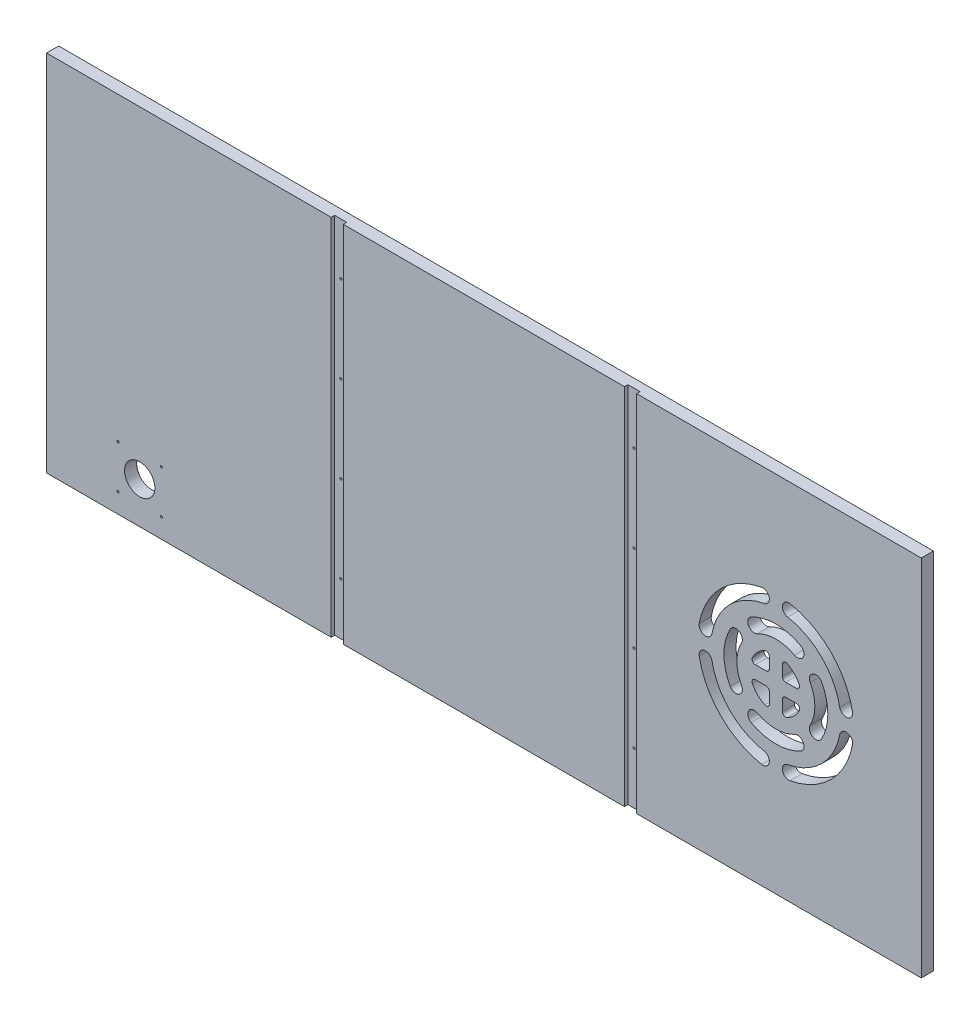
SolidWorks part; units mm, degrees
material "Pine"
ref_plane "Front Plane" through (0, 0, 0) normal (0, 0, 1) x (1, 0, 0)
ref_plane "Top Plane" through (0, 0, 0) normal (0, 1, 0) x (1, 0, 0)
ref_plane "Right Plane" through (0, 0, 0) normal (1, 0, 0) x (0, 0, -1)
sketch "Sketch1" plane through (0, 0, 0) normal (0, 0, 1) x (1, 0, 0)
  line L0 (8932.6508, -5243.5125) -> (10226.1458, -5243.5125)
  line L1 (9086.3208, -4722.0918) -> (10222.9708, -4853.7812)
  line L2 (8914.8708, -6342.0625) -> (10197.5708, -6342.0625)
  line L3 (8914.8708, -5808.6625) -> (10197.5708, -5808.6625)
  line L4 (8919.6333, -5253.0375) -> (10218.2083, -5253.0375)
  line L5 (9134.2633, -4656.1375) -> (9134.2633, -4638.3575)
  line L6 (9091.0833, -4638.3575) -> (9134.2633, -4638.3575)
  line L7 (9091.0833, -4567.2375) -> (9091.0833, -4638.3575)
  line L8 (9134.2633, -4656.1375) -> (9581.3033, -4656.1375)
  line L9 (9091.0833, -4567.2375) -> (9624.4833, -4567.2375)
  line L10 (9581.3033, -4656.1375) -> (9581.3033, -4638.3575)
  line L11 (9581.3033, -4638.3575) -> (9624.4833, -4638.3575)
  line L12 (9624.4833, -4567.2375) -> (9624.4833, -4638.3575)
  line L13 (8932.6508, -5225.7325) -> (9344.9775, -5225.7325)
  line L14 (8932.6508, -5256.2125) -> (8932.6508, -5243.5125)
  line L15 (8911.6958, -5256.2125) -> (8932.6508, -5256.2125)
  line L16 (8914.8708, -4722.0918) -> (9086.3208, -4722.0918)
  line L17 (8911.6958, -4715.5913) -> (8932.6508, -4715.5913)
  line L18 (8914.8708, -6342.0625) -> (8914.8708, -5808.6625)
  line L19 (12082.9917, -4722.0918) -> (10946.3417, -4853.7812)
  line L20 (12236.6617, -5243.5125) -> (10943.1667, -5243.5125)
  line L21 (10951.1042, -5253.0375) -> (12249.6792, -5253.0375)
  line L22 (10838.3917, -5656.2625) -> (11308.2917, -5656.2625)
  line L23 (10838.3917, -5719.7625) -> (11308.2917, -5719.7625)
  line L24 (10838.3917, -5742.5368) -> (11308.2917, -5742.5368)
  line L25 (10806.6417, -6342.0625) -> (11340.0417, -6342.0625)
  line L26 (10803.4667, -6335.7125) -> (11343.2167, -6335.7125)
  line L27 (10803.4667, -6317.9325) -> (11343.2167, -6317.9325)
  line L28 (10943.1667, -5225.7325) -> (11376.4483, -5225.7325)
  line L29 (11506.7292, -4754.5625) -> (10806.6417, -4827.5875)
  line L30 (11506.7292, -4567.2375) -> (11506.7292, -4754.5625)
  line L31 (10806.6417, -4567.2375) -> (10806.6417, -4827.5875)
  line L32 (10806.6417, -4567.2375) -> (11506.7292, -4567.2375)
  line L33 (10235.6708, -6329.3625) -> (10245.1958, -6329.3625)
  line L34 (10245.1958, -6329.3625) -> (10254.7208, -6278.5625)
  line L35 (10302.3458, -6329.3625) -> (10311.8708, -6278.5625)
  line L36 (10302.3458, -6329.3625) -> (10292.8208, -6329.3625)
  line L37 (10245.1958, -5821.3625) -> (10254.7208, -5872.1625)
  line L38 (10235.6708, -5821.3625) -> (10245.1958, -5821.3625)
  line L39 (10292.8208, -5821.3625) -> (10302.3458, -5821.3625)
  line L40 (10302.3458, -5821.3625) -> (10311.8708, -5872.1625)
  line L41 (10235.6708, -5821.3625) -> (10235.6708, -6329.3625)
  line L42 (10254.7208, -5872.1625) -> (10254.7208, -6278.5625)
  line L43 (10311.8708, -5872.1625) -> (10311.8708, -6278.5625)
  line L44 (10292.8208, -5821.3625) -> (10292.8208, -6329.3625)
  line L45 (8932.6508, -5225.7325) -> (8932.6508, -4715.5913)
  line L46 (8911.6958, -4715.5913) -> (8911.6958, -5256.2125)
  line L47 (8914.8708, -5248.275) -> (8914.8708, -4722.0918)
  line L48 (8919.6333, -5253.0375) -> (8914.8708, -5248.275)
  line L49 (8914.8708, -5145.0875) -> (8937.426, -5145.0875)
  line L50 (8914.8708, -5202.2375) -> (8937.426, -5202.2375)
  line L51 (10838.3917, -5656.2625) -> (10838.3917, -5719.7625)
  line L52 (10832.0417, -5736.1868) -> (10856.1717, -5736.1868)
  line L53 (10806.6417, -6342.0625) -> (10806.6417, -5818.7368)
  line L54 (10832.0417, -5649.9125) -> (10856.1717, -5649.9125)
  line L55 (10832.0417, -5726.1125) -> (10856.1717, -5726.1125)
  line L56 (10806.6417, -5818.7368) -> (10833.9015, -5818.7368)
  line L57 (10832.0417, -5806.0442) -> (10851.6815, -5806.0442)
  line L58 (10856.1717, -5801.5541) -> (10856.1717, -5736.1868)
  line L59 (10838.3917, -5814.2467) -> (10838.3917, -5742.5368)
  line L60 (10832.0417, -5806.0442) -> (10832.0417, -5736.1868)
  line L61 (10803.4667, -6317.9325) -> (10803.4667, -6335.7125)
  line L62 (10197.5708, -5808.6625) -> (10197.5708, -6342.0625)
  line L63 (9762.3842, -6348.4125) -> (9762.3842, -5802.3125)
  line L64 (9780.1642, -6348.4125) -> (9762.3842, -6348.4125)
  line L65 (9780.1642, -5802.3125) -> (9780.1642, -6348.4125)
  line L66 (9762.3842, -5802.3125) -> (9780.1642, -5802.3125)
  line L67 (9332.2775, -6348.4125) -> (9332.2775, -5802.3125)
  line L68 (9332.2775, -6348.4125) -> (9350.0575, -6348.4125)
  line L69 (9350.0575, -5802.3125) -> (9350.0575, -6348.4125)
  line L70 (9332.2775, -5802.3125) -> (9350.0575, -5802.3125)
  line L71 (9993.8374, -6061.075) -> (9993.8374, -6045.2418)
  line L72 (9998.5999, -6065.8375) -> (10014.4331, -6065.8375)
  line L73 (9998.5999, -6084.8875) -> (10014.4331, -6084.8875)
  line L74 (9993.8374, -6105.4832) -> (9993.8374, -6089.65)
  line L75 (9974.7874, -6105.4832) -> (9974.7874, -6089.65)
  line L76 (9954.1917, -6084.8875) -> (9970.0249, -6084.8875)
  line L77 (9974.7874, -6061.075) -> (9974.7874, -6045.2418)
  line L78 (9954.1917, -6065.8375) -> (9970.0249, -6065.8375)
  line L79 (10793.9417, -6237.2875) -> (10816.4969, -6237.2875)
  line L80 (10793.9417, -6294.4375) -> (10816.4969, -6294.4375)
  line L81 (10856.1717, -5649.9125) -> (10856.1717, -5726.1125)
  line L82 (10832.0417, -5726.1125) -> (10832.0417, -5649.9125)
  line L83 (10226.1458, -5225.7325) -> (10226.1458, -5243.5125)
  line L84 (10205.1908, -5257.8) -> (10205.1908, -4844.2499)
  line L85 (10230.9083, -4844.2499) -> (10230.9083, -5257.8)
  line L86 (10205.1908, -5257.8) -> (10230.9083, -5257.8)
  line L87 (10205.1908, -4844.2499) -> (10230.9083, -4844.2499)
  line L88 (10946.3417, -5176.8375) -> (10968.8969, -5176.8375)
  line L89 (9349.4676, -5141.9125) -> (9358.2674, -5141.9125)
  line L90 (10946.3417, -5119.6875) -> (10968.8969, -5119.6875)
  line L91 (9929.011, -4660.9635) -> (10066.0807, -4660.9635)
  line L92 (9929.011, -4678.7435) -> (10066.0807, -4678.7435)
  line L93 (10943.1667, -5225.7325) -> (10943.1667, -5243.5125)
  line L94 (10946.3417, -5248.275) -> (10951.1042, -5253.0375)
  line L95 (10946.3417, -5257.8063) -> (10946.3417, -4849.0188)
  line L96 (10964.1217, -5257.8) -> (10964.1217, -4844.2499)
  line L97 (10938.4042, -4844.2499) -> (10938.4042, -5257.8)
  line L98 (10938.4042, -5257.8) -> (10964.1217, -5257.8)
  line L99 (10964.1217, -4844.2499) -> (10938.4042, -4844.2499)
  line L100 (10344.8908, -4560.8875) -> (10369.0208, -4560.8875)
  line L101 (10344.8908, -4560.8875) -> (10369.0208, -4560.8875)
  line L102 (10800.2917, -4560.8875) -> (10824.4217, -4560.8875)
  line L103 (10200.4156, -5119.6875) -> (10222.9708, -5119.6875)
  line L104 (10200.4156, -5176.8375) -> (10222.9708, -5176.8375)
  line L105 (9344.9775, -5146.4026) -> (9344.9775, -5225.7325)
  line L106 (10344.8908, -4560.8875) -> (10344.8908, -4833.9375)
  line L107 (9792.8642, -5225.7325) -> (9792.8642, -5146.4026)
  line L108 (9362.7575, -5225.7325) -> (9775.0842, -5225.7325)
  line L109 (9680.3633, -4761.8396) -> (9680.3633, -4559.9604)
  line L110 (9656.2333, -4559.9604) -> (9680.3633, -4559.9604)
  line L111 (9656.2333, -4761.8396) -> (9680.3633, -4761.8396)
  line L112 (9656.2333, -4761.8396) -> (9656.2333, -4559.9604)
  line L113 (9779.5743, -5141.9125) -> (9788.374, -5141.9125)
  line L114 (10070.5708, -4665.4536) -> (10070.5708, -4674.2534)
  line L115 (9924.5208, -4674.2534) -> (9924.5208, -4665.4536)
  line L116 (12127.4417, -6188.3925) -> (12205.5015, -6188.3925)
  line L117 (12209.9917, -6170.6125) -> (12209.9917, -6183.9024)
  line L118 (9792.8642, -5225.7325) -> (10226.1458, -5225.7325)
  line L119 (9662.5833, -4754.5625) -> (10362.6708, -4827.5875)
  line L120 (9662.5833, -4567.2375) -> (9662.5833, -4754.5625)
  line L121 (10362.6708, -4567.2375) -> (10362.6708, -4827.5875)
  line L122 (9662.5833, -4567.2375) -> (10362.6708, -4567.2375)
  line L123 (10824.4217, -4833.9375) -> (10800.2917, -4833.9375)
  line L124 (10800.2917, -4833.9375) -> (10800.2917, -4560.8875)
  line L125 (10824.4217, -4560.8875) -> (10824.4217, -4833.9375)
  line L126 (10344.8908, -4833.9375) -> (10369.0208, -4833.9375)
  line L127 (10369.0208, -4833.9375) -> (10369.0208, -4560.8875)
  line L128 (10222.9708, -5248.275) -> (10218.2083, -5253.0375)
  line L129 (10222.9708, -5257.8063) -> (10222.9708, -4849.0188)
  line L130 (11734.6544, -5701.375) -> (11739.2301, -5701.375)
  line L131 (9362.7575, -5225.7325) -> (9362.7575, -5146.4026)
  line L132 (9775.0842, -5146.4026) -> (9775.0842, -5225.7325)
  line L133 (11761.3864, -5701.375) -> (11756.8282, -5701.375)
  line L134 (11734.6544, -5693.755) -> (11739.2301, -5693.755)
  line L135 (11761.4039, -5693.755) -> (11756.8282, -5693.755)
  line L136 (11734.6544, -5701.375) -> (11739.2301, -5701.375)
  line L137 (11744.3462, -5721.3024) -> (11744.3462, -5706.4179)
  line L138 (11751.7122, -5721.3024) -> (11751.7122, -5706.4179)
  line L139 (11740.0917, -6170.6125) -> (11740.0917, -6183.9024)
  line L140 (11689.2917, -6188.3925) -> (11822.6417, -6188.3925)
  line L141 (11689.2917, -6348.4093) -> (11689.2917, -6164.2657)
  line L142 (11689.2917, -6164.2657) -> (11746.4417, -6164.2657)
  line L143 (11746.4417, -6164.2657) -> (11746.4417, -6188.3925)
  line L144 (11689.2917, -6164.2657) -> (11746.4417, -6164.2657)
  line L145 (11340.0417, -5818.7368) -> (11340.0417, -6342.0625)
  line L146 (11290.5117, -5726.1125) -> (11314.6417, -5726.1125)
  line L147 (11290.5117, -5649.9125) -> (11290.5117, -5726.1125)
  line L148 (11340.0417, -5818.7368) -> (11312.7818, -5818.7368)
  line L149 (11314.6417, -5806.0442) -> (11295.0018, -5806.0442)
  line L150 (11290.5117, -5801.5541) -> (11290.5117, -5736.1868)
  line L151 (11308.2917, -5814.2467) -> (11308.2917, -5742.5368)
  line L152 (11314.6417, -5806.0442) -> (11314.6417, -5736.1868)
  line L153 (11290.5117, -5736.1868) -> (11314.6417, -5736.1868)
  line L154 (11848.0417, -6267.1325) -> (11962.3417, -6267.1325)
  line L155 (11962.3417, -6267.1325) -> (11962.3417, -6203.6325)
  line L156 (11343.2167, -6317.9325) -> (11343.2167, -6335.7125)
  line L157 (11365.4417, -5656.2625) -> (11365.4417, -5719.7625)
  line L158 (11365.4417, -5656.2625) -> (11479.7417, -5656.2625)
  line L159 (11778.1917, -6071.3937) -> (11802.3217, -6071.3937)
  line L160 (11314.6417, -5726.1125) -> (11314.6417, -5649.9125)
  line L161 (11314.6417, -5649.9125) -> (11290.5117, -5649.9125)
  line L162 (11308.2917, -5719.7625) -> (11308.2917, -5656.2625)
  line L163 (11689.2917, -6348.4093) -> (11713.4217, -6348.4093)
  line L164 (12203.6417, -6164.2657) -> (12260.7917, -6164.2657)
  line L165 (11713.4217, -6348.4093) -> (11713.4217, -6164.2657)
  line L166 (11695.6417, -6342.0625) -> (11695.6417, -6170.6125)
  line L167 (11695.6417, -6048.5337) -> (11699.4517, -6052.3437)
  line L168 (11822.6417, -6292.5325) -> (11822.6417, -6188.3925)
  line L169 (11695.6417, -6342.0625) -> (11695.6417, -6170.6125)
  line L170 (11848.0417, -6203.6325) -> (11962.3417, -6203.6325)
  line L171 (11848.0417, -6203.6325) -> (11848.0417, -6267.1325)
  line L172 (11987.7417, -6267.1325) -> (11987.7417, -6203.6325)
  line L173 (11784.5417, -6077.7437) -> (11784.5417, -6141.2438)
  line L174 (11517.8417, -5656.2625) -> (11632.1417, -5656.2625)
  line L175 (11632.1417, -5656.2625) -> (11632.1417, -5719.7625)
  line L176 (11632.1417, -5719.7625) -> (11517.8417, -5719.7625)
  line L177 (11517.8417, -5719.7625) -> (11517.8417, -5656.2625)
  line L178 (11692.4667, -6028.2137) -> (11692.4667, -6045.9937)
  line L179 (11695.6417, -5979.3188) -> (11718.1969, -5979.3188)
  line L180 (11695.6417, -5922.1687) -> (11718.1969, -5922.1687)
  line L181 (11821.0415, -5722.9375) -> (11821.0415, -5943.6)
  line L182 (11687.7042, -5651.5) -> (11701.9917, -5651.5)
  line L183 (11687.7042, -5651.5) -> (11687.7042, -6055.5251)
  line L184 (11687.7042, -6055.5251) -> (11701.9917, -6055.5251)
  line L185 (11701.9917, -6055.5251) -> (11701.9917, -5651.5)
  line L186 (11695.6417, -6055.2013) -> (11695.6417, -5649.595)
  line L187 (11695.6417, -5656.2625) -> (11695.6417, -6048.5337)
  line L188 (11695.6417, -6170.6125) -> (11740.0917, -6170.6125)
  line L189 (12203.6417, -6164.2657) -> (12203.6417, -6188.3925)
  line L190 (12254.4417, -6342.0625) -> (12254.4417, -6170.6125)
  line L191 (12129.0419, -5943.6) -> (12129.0419, -5722.9375)
  line L192 (12254.4417, -6048.5337) -> (12250.6317, -6052.3437)
  line L193 (12257.6167, -6045.9937) -> (12257.6167, -6028.2137)
  line L194 (12248.0917, -5651.5) -> (12262.3792, -5651.5)
  line L195 (12262.3792, -5651.5) -> (12262.3792, -6055.5251)
  line L196 (12262.3792, -6055.5251) -> (12248.0917, -6055.5251)
  line L197 (12248.0917, -6055.5251) -> (12248.0917, -5651.5)
  line L198 (12254.4417, -6141.2438) -> (12254.4417, -6077.7437)
  line L199 (12236.6617, -6164.2657) -> (12260.7917, -6164.2657)
  line L200 (12102.0417, -6267.1325) -> (11987.7417, -6267.1325)
  line L201 (11330.1865, -6237.2875) -> (11352.7417, -6237.2875)
  line L202 (11330.1865, -6294.4375) -> (11352.7417, -6294.4375)
  line L203 (11474.6617, -5851.8425) -> (11492.4417, -5851.8425)
  line L204 (11474.6617, -5808.6625) -> (11474.6617, -5851.8425)
  line L205 (11403.5417, -5808.6625) -> (11474.6617, -5808.6625)
  line L206 (11492.4417, -5851.8425) -> (11492.4417, -6298.8825)
  line L207 (11403.5417, -6342.0625) -> (11403.5417, -5808.6625)
  line L208 (11474.6617, -6298.8825) -> (11492.4417, -6298.8825)
  line L209 (11474.6617, -6342.0625) -> (11474.6617, -6298.8825)
  line L210 (11403.5417, -6342.0625) -> (11474.6617, -6342.0625)
  line L211 (11619.4417, -5851.8425) -> (11601.6617, -5851.8425)
  line L212 (11601.6617, -5808.6625) -> (11601.6617, -5851.8425)
  line L213 (11530.5417, -5808.6625) -> (11601.6617, -5808.6625)
  line L214 (11619.4417, -5851.8425) -> (11619.4417, -6298.8825)
  line L215 (11530.5417, -6342.0625) -> (11530.5417, -5808.6625)
  line L216 (11619.4417, -6298.8825) -> (11601.6617, -6298.8825)
  line L217 (11601.6617, -6342.0625) -> (11601.6617, -6298.8825)
  line L218 (11530.5417, -6342.0625) -> (11601.6617, -6342.0625)
  line L219 (11479.7417, -5719.7625) -> (11479.7417, -5656.2625)
  line L220 (11365.4417, -5719.7625) -> (11479.7417, -5719.7625)
  line L221 (11778.1917, -6147.5937) -> (11802.3217, -6147.5937)
  line L222 (11802.3217, -6071.3937) -> (11802.3217, -6147.5937)
  line L223 (11778.1917, -6147.5937) -> (11778.1917, -6071.3937)
  line L224 (12254.4417, -5922.1687) -> (12231.8865, -5922.1687)
  line L225 (12254.4417, -5979.3188) -> (12231.8865, -5979.3188)
  line L226 (12254.4417, -6055.2013) -> (12254.4417, -5649.595)
  line L227 (12254.4417, -6048.5337) -> (12254.4417, -5656.2625)
  line L228 (11841.6917, -5702.2873) -> (12108.3917, -5702.2873)
  line L229 (11822.6417, -6292.5325) -> (12127.4417, -6292.5325)
  line L230 (12127.4417, -6292.5325) -> (12127.4417, -6188.3925)
  line L231 (12254.4417, -6170.6125) -> (12209.9917, -6170.6125)
  line L232 (11695.6417, -6342.0625) -> (12254.4417, -6342.0625)
  line L233 (12236.6617, -6348.4093) -> (12260.7917, -6348.4093)
  line L234 (12260.7917, -6348.4093) -> (12260.7917, -6164.2657)
  line L235 (12236.6617, -6348.4093) -> (12236.6617, -6164.2657)
  line L236 (12102.0417, -6203.6325) -> (12102.0417, -6267.1325)
  line L237 (11987.7417, -6203.6325) -> (12102.0417, -6203.6325)
  line L238 (12236.6617, -6147.5937) -> (12236.6617, -6071.3937)
  line L239 (12203.6417, -6188.3925) -> (12260.7917, -6188.3925)
  line L240 (11098.7417, -4665.4536) -> (11098.7417, -4674.2534)
  line L241 (11394.2283, -5146.4026) -> (11394.2283, -5225.7325)
  line L242 (11376.4483, -5225.7325) -> (11376.4483, -5146.4026)
  line L243 (11394.2283, -5225.7325) -> (11806.555, -5225.7325)
  line L244 (11841.6917, -5964.2502) -> (12108.3917, -5964.2502)
  line L245 (12236.6617, -6147.5937) -> (12260.7917, -6147.5937)
  line L246 (12236.6617, -5256.2125) -> (12236.6617, -5243.5125)
  line L247 (12260.7917, -6147.5937) -> (12260.7917, -6071.3937)
  line L248 (12260.7917, -6071.3937) -> (12236.6617, -6071.3937)
  line L249 (12254.4417, -6077.7437) -> (11784.5417, -6077.7437)
  line L250 (11784.5417, -6141.2438) -> (12254.4417, -6141.2438)
  line L252 (12254.4417, -5656.2625) -> (11695.6417, -5656.2625)
  line L253 (11699.4517, -6052.3437) -> (12250.6317, -6052.3437)
  line L254 (11692.4667, -6045.9937) -> (12257.6167, -6045.9937)
  line L255 (11692.4667, -6028.2137) -> (12257.6167, -6028.2137)
  line L256 (11824.335, -5146.4026) -> (11824.335, -5225.7325)
  line L257 (11811.0451, -5141.9125) -> (11819.8449, -5141.9125)
  line L258 (11244.7917, -4674.2534) -> (11244.7917, -4665.4536)
  line L259 (11806.555, -5225.7325) -> (11806.555, -5146.4026)
  line L260 (11488.9492, -4761.8396) -> (11488.9492, -4559.9604)
  line L261 (11488.9492, -4559.9604) -> (11513.0792, -4559.9604)
  line L262 (11488.9492, -4761.8396) -> (11513.0792, -4761.8396)
  line L263 (11513.0792, -4761.8396) -> (11513.0792, -4559.9604)
  line L264 (11240.3015, -4660.9635) -> (11103.2318, -4660.9635)
  line L265 (11103.2318, -4678.7435) -> (11240.3015, -4678.7435)
  line L266 (12236.6617, -5225.7325) -> (12236.6617, -4715.5913)
  line L267 (12257.6167, -4715.5913) -> (12257.6167, -5256.2125)
  line L268 (12254.4417, -5248.275) -> (12254.4417, -4722.0918)
  line L269 (12236.6617, -5225.7325) -> (11824.335, -5225.7325)
  line L270 (12035.0492, -4656.1375) -> (12035.0492, -4638.3575)
  line L271 (12078.2292, -4638.3575) -> (12035.0492, -4638.3575)
  line L272 (12078.2292, -4567.2375) -> (12078.2292, -4638.3575)
  line L273 (12035.0492, -4656.1375) -> (11588.0092, -4656.1375)
  line L274 (11544.8292, -4567.2375) -> (12078.2292, -4567.2375)
  line L275 (11588.0092, -4656.1375) -> (11588.0092, -4638.3575)
  line L276 (11544.8292, -4638.3575) -> (11588.0092, -4638.3575)
  line L277 (11544.8292, -4567.2375) -> (11544.8292, -4638.3575)
  line L278 (12249.6792, -5253.0375) -> (12254.4417, -5248.275)
  line L280 (12257.6167, -5256.2125) -> (12236.6617, -5256.2125)
  line L281 (12231.8865, -5145.0875) -> (12254.4417, -5145.0875)
  line L282 (12231.8865, -5202.2375) -> (12254.4417, -5202.2375)
  line L283 (12236.6617, -4715.5913) -> (12257.6167, -4715.5913)
  line L284 (12082.9917, -4722.0918) -> (12254.4417, -4722.0918)
  line L285 (11380.9385, -5141.9125) -> (11389.7382, -5141.9125)
  circle A0 centre (8923.7608, -4778.9042) radius 1.5875
  circle A1 centre (9062.6598, -4736.3765) radius 2.3685
  circle A2 centre (9051.3958, -6281.7375) radius 22.225
  circle A3 centre (9083.1458, -6249.9875) radius 1.5875
  circle A4 centre (9083.1458, -6313.4875) radius 1.5875
  circle A5 centre (9019.6458, -6249.9875) radius 1.5875
  circle A6 centre (9019.6458, -6313.4875) radius 1.5875
  circle A7 centre (8972.3383, -5202.2375) radius 1.5875
  circle A8 centre (8923.7608, -5015.9708) radius 1.5875
  circle A9 centre (8923.7608, -5134.5042) radius 1.5875
  circle A10 centre (9054.5708, -5234.6225) radius 1.5875
  circle A11 centre (8923.7608, -4897.4375) radius 1.5875
  circle A12 centre (8972.3383, -5087.9375) radius 1.5875
  circle A13 centre (8972.3383, -5145.0875) radius 1.5875
  circle A14 centre (10847.2817, -5668.9625) radius 1.5875
  circle A15 centre (10847.2817, -5707.0625) radius 1.5875
  circle A16 centre (10847.2817, -5755.2368) radius 1.5875
  circle A17 centre (10851.4092, -6237.2875) radius 1.5875
  circle A18 centre (10851.4092, -6294.4375) radius 1.5875
  circle A19 centre (10847.2817, -5793.3442) radius 1.5875
  arc A20 (10833.9015, -5818.7368) -> (10838.3917, -5814.2467) centre (10836.1466, -5816.4918) ccw
  arc A21 (10851.6815, -5806.0442) -> (10856.1717, -5801.5541) centre (10853.9266, -5803.7992) ccw
  circle A22 centre (10882.8417, -6040.4375) radius 1.5875
  circle A23 centre (10882.8417, -6218.2375) radius 1.5875
  circle A24 centre (10882.8417, -5862.6375) radius 1.5875
  circle A25 centre (10908.2417, -6326.8225) radius 1.5875
  circle A26 centre (10908.2417, -6326.8225) radius 1.5875
  circle A27 centre (10851.4092, -6180.1375) radius 1.5875
  circle A28 centre (10815.5317, -4783.4231) radius 1.5875
  circle A29 centre (10815.5317, -4696.9488) radius 1.5875
  circle A30 centre (10815.5317, -4610.4746) radius 1.5875
  circle A31 centre (10979.1323, -4867.0082) radius 2.3685
  circle A32 centre (10190.1802, -4867.0082) radius 2.3685
  circle A33 centre (10955.2317, -4929.9812) radius 1.5875
  circle A34 centre (10955.2317, -5031.5812) radius 1.5875
  circle A35 centre (10214.0808, -4929.9812) radius 1.5875
  circle A36 centre (10214.0808, -5031.5812) radius 1.5875
  circle A37 centre (9341.1675, -6265.8625) radius 1.5875
  circle A38 centre (9771.2742, -5884.8625) radius 1.5875
  circle A39 centre (9771.2742, -6138.8625) radius 1.5875
  circle A40 centre (9771.2742, -6011.8625) radius 1.5875
  arc A41 (10036.2287, -6113.8083) -> (10051.3426, -6111.6033) centre (10042.9639, -6107.0732) ccw
  arc A42 (10051.3426, -6111.6033) -> (10051.3426, -6039.1217) centre (9984.3124, -6075.3625) ccw
  arc A43 (10051.3426, -6039.1217) -> (10036.2287, -6036.9167) centre (10042.9639, -6043.6518) ccw
  arc A44 (10034.5851, -6102.5431) -> (10034.5851, -6048.1819) centre (9984.3124, -6075.3625) ccw
  arc A45 (10034.5851, -6102.5431) -> (10036.2287, -6113.8083) centre (10042.9639, -6107.0732) ccw
  arc A46 (10036.2287, -6036.9167) -> (10034.5851, -6048.1819) centre (10042.9639, -6043.6518) ccw
  arc A47 (9945.8666, -6127.2787) -> (9948.0717, -6142.3927) centre (9952.6018, -6134.0139) ccw
  arc A48 (9948.0717, -6142.3927) -> (10020.5532, -6142.3927) centre (9984.3124, -6075.3625) ccw
  arc A49 (10020.5532, -6142.3927) -> (10022.7583, -6127.2787) centre (10016.0231, -6134.0139) ccw
  arc A50 (9957.1319, -6125.6352) -> (10011.493, -6125.6352) centre (9984.3124, -6075.3625) ccw
  arc A51 (9957.1319, -6125.6352) -> (9945.8666, -6127.2787) centre (9952.6018, -6134.0139) ccw
  arc A52 (10022.7583, -6127.2787) -> (10011.493, -6125.6352) centre (10016.0231, -6134.0139) ccw
  arc A53 (9932.3962, -6036.9167) -> (9917.2822, -6039.1217) centre (9925.661, -6043.6518) ccw
  arc A54 (9917.2822, -6039.1217) -> (9917.2822, -6111.6033) centre (9984.3124, -6075.3625) ccw
  arc A55 (9917.2822, -6111.6033) -> (9932.3962, -6113.8083) centre (9925.661, -6107.0732) ccw
  arc A56 (9934.0398, -6048.1819) -> (9934.0398, -6102.5431) centre (9984.3124, -6075.3625) ccw
  arc A57 (9934.0398, -6048.1819) -> (9932.3962, -6036.9167) centre (9925.661, -6043.6518) ccw
  arc A58 (9932.3962, -6113.8083) -> (9934.0398, -6102.5431) centre (9925.661, -6107.0732) ccw
  arc A59 (9945.8666, -6023.4463) -> (9957.1319, -6025.0898) centre (9952.6018, -6016.7111) ccw
  arc A60 (10011.493, -6025.0898) -> (10022.7583, -6023.4463) centre (10016.0231, -6016.7111) ccw
  arc A61 (10011.493, -6025.0898) -> (9957.1319, -6025.0898) centre (9984.3124, -6075.3625) ccw
  arc A62 (9948.0717, -6008.3323) -> (9945.8666, -6023.4463) centre (9952.6018, -6016.7111) ccw
  arc A63 (10020.5532, -6008.3323) -> (9948.0717, -6008.3323) centre (9984.3124, -6075.3625) ccw
  arc A64 (10022.7583, -6023.4463) -> (10020.5532, -6008.3323) centre (10016.0231, -6016.7111) ccw
  arc A65 (10005.0943, -6187.7574) -> (10096.7073, -6096.1443) centre (9984.3124, -6075.3625) ccw
  arc A66 (9993.8374, -6178.3911) -> (10005.0943, -6187.7574) centre (10003.3624, -6178.3911) ccw
  arc A67 (10001.6306, -6169.0249) -> (10077.9748, -6092.6807) centre (9984.3124, -6075.3625) ccw
  arc A68 (10087.3411, -6084.8875) -> (10077.9748, -6092.6807) centre (10087.3411, -6094.4125) ccw
  arc A69 (10001.6306, -6169.0249) -> (9993.8374, -6178.3911) centre (10003.3624, -6178.3911) ccw
  arc A70 (9963.5306, -6187.7574) -> (9974.7874, -6178.3911) centre (9965.2624, -6178.3911) ccw
  arc A71 (9871.9176, -6096.1443) -> (9963.5306, -6187.7574) centre (9984.3124, -6075.3625) ccw
  arc A72 (9881.2838, -6084.8875) -> (9871.9176, -6096.1443) centre (9881.2838, -6094.4125) ccw
  arc A73 (9890.65, -6092.6807) -> (9966.9943, -6169.0249) centre (9984.3124, -6075.3625) ccw
  arc A74 (9974.7874, -6178.3911) -> (9966.9943, -6169.0249) centre (9965.2624, -6178.3911) ccw
  arc A75 (9890.65, -6092.6807) -> (9881.2838, -6084.8875) centre (9881.2838, -6094.4125) ccw
  arc A76 (9871.9176, -6054.5807) -> (9881.2838, -6065.8375) centre (9881.2838, -6056.3125) ccw
  arc A77 (9963.5306, -5962.9676) -> (9871.9176, -6054.5807) centre (9984.3124, -6075.3625) ccw
  arc A78 (9974.7874, -5972.3339) -> (9963.5306, -5962.9676) centre (9965.2624, -5972.3339) ccw
  arc A79 (9966.9943, -5981.7001) -> (9890.65, -6058.0443) centre (9984.3124, -6075.3625) ccw
  arc A80 (9881.2838, -6065.8375) -> (9890.65, -6058.0443) centre (9881.2838, -6056.3125) ccw
  arc A81 (9966.9943, -5981.7001) -> (9974.7874, -5972.3339) centre (9965.2624, -5972.3339) ccw
  arc A82 (10077.9748, -6058.0443) -> (10087.3411, -6065.8375) centre (10087.3411, -6056.3125) ccw
  arc A83 (9993.8374, -5972.3339) -> (10001.6306, -5981.7001) centre (10003.3624, -5972.3339) ccw
  arc A84 (10077.9748, -6058.0443) -> (10001.6306, -5981.7001) centre (9984.3124, -6075.3625) ccw
  arc A85 (10087.3411, -6065.8375) -> (10096.7073, -6054.5807) centre (10087.3411, -6056.3125) ccw
  arc A86 (10096.7073, -6054.5807) -> (10005.0943, -5962.9676) centre (9984.3124, -6075.3625) ccw
  arc A87 (10005.0943, -5962.9676) -> (9993.8374, -5972.3339) centre (10003.3624, -5972.3339) ccw
  arc A88 (10014.4331, -6065.8375) -> (10018.7361, -6059.0339) centre (10014.4331, -6061.075) ccw
  arc A89 (10018.7361, -6059.0339) -> (10000.641, -6040.9388) centre (9984.3124, -6075.3625) ccw
  arc A90 (10000.641, -6040.9388) -> (9993.8374, -6045.2418) centre (9998.5999, -6045.2418) ccw
  arc A91 (9993.8374, -6061.075) -> (9998.5999, -6065.8375) centre (9998.5999, -6061.075) ccw
  arc A92 (9993.8374, -6105.4832) -> (10000.641, -6109.7862) centre (9998.5999, -6105.4832) ccw
  arc A93 (10000.641, -6109.7862) -> (10018.7361, -6091.6911) centre (9984.3124, -6075.3625) ccw
  arc A94 (10018.7361, -6091.6911) -> (10014.4331, -6084.8875) centre (10014.4331, -6089.65) ccw
  arc A95 (9998.5999, -6084.8875) -> (9993.8374, -6089.65) centre (9998.5999, -6089.65) ccw
  arc A96 (9954.1917, -6084.8875) -> (9949.8888, -6091.6911) centre (9954.1917, -6089.65) ccw
  arc A97 (9949.8888, -6091.6911) -> (9967.9839, -6109.7862) centre (9984.3124, -6075.3625) ccw
  arc A98 (9967.9839, -6109.7862) -> (9974.7874, -6105.4832) centre (9970.0249, -6105.4832) ccw
  arc A99 (9974.7874, -6089.65) -> (9970.0249, -6084.8875) centre (9970.0249, -6089.65) ccw
  arc A100 (9970.0249, -6065.8375) -> (9974.7874, -6061.075) centre (9970.0249, -6061.075) ccw
  arc A101 (9949.8888, -6059.0339) -> (9954.1917, -6065.8375) centre (9954.1917, -6061.075) ccw
  arc A102 (9967.9839, -6040.9388) -> (9949.8888, -6059.0339) centre (9984.3124, -6075.3625) ccw
  arc A103 (9974.7874, -6045.2418) -> (9967.9839, -6040.9388) centre (9970.0249, -6045.2418) ccw
  arc A104 (10096.7073, -6096.1443) -> (10087.3411, -6084.8875) centre (10087.3411, -6094.4125) ccw
  circle A105 centre (9771.2742, -6265.8625) radius 1.5875
  circle A106 centre (9341.1675, -5884.8625) radius 1.5875
  circle A107 centre (9341.1675, -6138.8625) radius 1.5875
  circle A108 centre (9341.1675, -6011.8625) radius 1.5875
  circle A109 centre (11037.2315, -4887.5494) radius 15.0812
  arc A110 (9349.4676, -5141.9125) -> (9344.9775, -5146.4026) centre (9347.2226, -5144.1576) ccw
  arc A111 (9362.7575, -5146.4026) -> (9358.2674, -5141.9125) centre (9360.5124, -5144.1576) ccw
  circle A112 centre (9946.7458, -4669.8535) radius 1.5875
  arc A113 (9924.5208, -4674.2534) -> (9929.011, -4678.7435) centre (9926.7659, -4676.4984) ccw
  circle A114 centre (11003.8092, -5176.8375) radius 1.5875
  circle A115 centre (11003.8092, -5119.6875) radius 1.5875
  circle A116 centre (10353.7808, -4696.9488) radius 1.5875
  circle A117 centre (10353.7808, -4610.4746) radius 1.5875
  circle A118 centre (10353.7808, -4783.4231) radius 1.5875
  circle A119 centre (11003.8092, -5062.5375) radius 1.5875
  circle A120 centre (9353.8675, -5160.9625) radius 1.5875
  circle A121 centre (9638.7708, -5234.6225) radius 1.5875
  circle A122 centre (9671.4733, -4724.1144) radius 1.5875
  circle A123 centre (9671.4733, -4661.3637) radius 1.5875
  circle A124 centre (9671.4733, -4598.6129) radius 1.5875
  arc A125 (9792.8642, -5146.4026) -> (9788.374, -5141.9125) centre (9790.6191, -5144.1576) ccw
  arc A126 (9779.5743, -5141.9125) -> (9775.0842, -5146.4026) centre (9777.3292, -5144.1576) ccw
  circle A127 centre (10048.3458, -4669.8535) radius 1.5875
  arc A128 (10070.5708, -4665.4536) -> (10066.0807, -4660.9635) centre (10068.3258, -4663.2086) ccw
  arc A129 (10066.0807, -4678.7435) -> (10070.5708, -4674.2534) centre (10068.3258, -4676.4984) ccw
  circle A130 centre (9997.5458, -4669.8535) radius 1.5875
  arc A131 (9929.011, -4660.9635) -> (9924.5208, -4665.4536) centre (9926.7659, -4663.2086) ccw
  circle A132 centre (10132.081, -4887.5494) radius 15.0812
  circle A133 centre (10165.5033, -5176.8375) radius 1.5875
  circle A134 centre (10165.5033, -5119.6875) radius 1.5875
  circle A135 centre (9486.3708, -5234.6225) radius 1.5875
  circle A136 centre (10165.5033, -5062.5375) radius 1.5875
  circle A137 centre (9206.9708, -5234.6225) radius 1.5875
  circle A138 centre (10070.5708, -5234.6225) radius 1.5875
  circle A139 centre (9918.1708, -5234.6225) radius 1.5875
  circle A140 centre (9783.9742, -5160.9625) radius 1.5875
  circle A141 centre (9783.9742, -5193.9825) radius 1.5875
  circle A142 centre (9353.8675, -5193.9825) radius 1.5875
  circle A143 centre (11073.3417, -6326.8225) radius 1.5875
  circle A144 centre (11073.3417, -6326.8225) radius 1.5875
  circle A145 centre (11295.2742, -6180.1375) radius 1.5875
  circle A146 centre (11295.2742, -6294.4375) radius 1.5875
  circle A147 centre (11295.2742, -6237.2875) radius 1.5875
  circle A148 centre (11975.0417, -5692.775) radius 3.4925
  circle A149 centre (11263.8417, -5862.6375) radius 1.5875
  arc A150 (11739.2301, -5701.375) -> (11744.3462, -5706.4179) centre (11748.0292, -5697.565) ccw
  arc A151 (11751.7122, -5706.4179) -> (11756.8282, -5701.375) centre (11748.0292, -5697.565) ccw
  arc A152 (11744.3462, -5721.3024) -> (11751.7122, -5721.3024) centre (11748.0292, -5725.505) ccw
  arc A153 (11734.6544, -5693.755) -> (11724.9787, -5697.565) centre (11730.5667, -5697.565) ccw
  arc A154 (11756.8282, -5693.755) -> (11739.2301, -5693.755) centre (11748.0292, -5697.565) ccw
  arc A155 (11724.9787, -5697.565) -> (11734.6544, -5701.375) centre (11730.5667, -5697.565) ccw
  arc A156 (11761.3864, -5701.375) -> (11771.0797, -5697.565) centre (11765.4842, -5697.565) ccw
  arc A157 (11771.0797, -5697.565) -> (11761.4039, -5693.755) centre (11765.4917, -5697.565) ccw
  arc A158 (11740.0917, -6183.9024) -> (11744.5818, -6188.3925) centre (11742.3367, -6186.1474) ccw
  arc A159 (12205.5015, -6188.3925) -> (12209.9917, -6183.9024) centre (12207.7466, -6186.1474) ccw
  circle A160 centre (11299.4017, -5793.3442) radius 1.5875
  arc A161 (11308.2917, -5814.2467) -> (11312.7818, -5818.7368) centre (11310.5367, -5816.4918) ccw
  arc A162 (11290.5117, -5801.5541) -> (11295.0018, -5806.0442) centre (11292.7567, -5803.7992) ccw
  circle A163 centre (11704.5317, -6314.149) radius 1.5875
  circle A164 centre (11748.9817, -6208.7125) radius 1.5875
  circle A165 centre (11263.8417, -6218.2375) radius 1.5875
  circle A166 centre (11263.8417, -6040.4375) radius 1.5875
  circle A167 centre (11238.4417, -6326.8225) radius 1.5875
  circle A168 centre (11238.4417, -6326.8225) radius 1.5875
  circle A169 centre (11299.4017, -5668.9625) radius 1.5875
  circle A170 centre (11299.4017, -5707.0625) radius 1.5875
  circle A171 centre (11726.7567, -6179.5025) radius 1.5875
  circle A172 centre (11704.5317, -6199.3198) radius 1.5875
  circle A173 centre (11748.9817, -6272.2125) radius 1.5875
  circle A174 centre (11704.5317, -6256.7344) radius 1.5875
  circle A175 centre (11299.4017, -5755.2368) radius 1.5875
  circle A176 centre (11913.4467, -6301.4225) radius 1.5875
  circle A177 centre (11790.2567, -6301.4225) radius 1.5875
  circle A178 centre (11793.4317, -6128.5437) radius 1.5875
  circle A179 centre (11753.1092, -5865.0188) radius 1.5875
  circle A180 centre (11809.9417, -6037.1038) radius 1.5875
  circle A181 centre (11809.9417, -6037.1038) radius 1.5875
  circle A182 centre (11753.1092, -5922.1687) radius 1.5875
  circle A183 centre (11975.0417, -5973.7625) radius 3.4925
  circle A184 centre (11975.0417, -6037.1038) radius 1.5875
  circle A185 centre (11753.1092, -5979.3188) radius 1.5875
  circle A186 centre (11975.0417, -6037.1038) radius 1.5875
  arc A187 (11841.6917, -5702.2873) -> (11821.0415, -5722.9375) centre (11841.6917, -5722.9375) ccw
  circle A188 centre (11811.5292, -5833.2687) radius 3.4925
  arc A189 (11821.0415, -5943.6) -> (11841.6917, -5964.2502) centre (11841.6917, -5943.6) ccw
  circle A190 centre (12196.9742, -5865.0188) radius 1.5875
  arc A191 (12129.0419, -5722.9375) -> (12108.3917, -5702.2873) centre (12108.3917, -5722.9375) ccw
  circle A192 centre (12036.6367, -6301.4225) radius 1.5875
  circle A193 centre (12159.8267, -6301.4225) radius 1.5875
  circle A194 centre (12138.5542, -5833.2687) radius 3.4925
  circle A195 centre (12197.2917, -5761.0375) radius 15.0812
  circle A196 centre (11793.4317, -6090.4437) radius 1.5875
  circle A197 centre (12196.9742, -5922.1687) radius 1.5875
  arc A198 (12108.3917, -5964.2502) -> (12129.0419, -5943.6) centre (12108.3917, -5943.6) ccw
  circle A199 centre (12196.9742, -5979.3188) radius 1.5875
  circle A200 centre (12201.1017, -6272.2125) radius 1.5875
  circle A201 centre (12245.5517, -6314.149) radius 1.5875
  circle A202 centre (12245.5517, -6256.7344) radius 1.5875
  circle A203 centre (12201.1017, -6208.7125) radius 1.5875
  circle A204 centre (12223.3267, -6179.5025) radius 1.5875
  circle A205 centre (12245.5517, -6199.3198) radius 1.5875
  circle A206 centre (11171.7667, -4669.8535) radius 1.5875
  circle A207 centre (11222.5667, -4669.8535) radius 1.5875
  arc A208 (11240.3015, -4678.7435) -> (11244.7917, -4674.2534) centre (11242.5466, -4676.4984) ccw
  circle A209 centre (11385.3383, -5193.9825) radius 1.5875
  circle A210 centre (12106.6527, -4736.3765) radius 2.3685
  circle A211 centre (12140.1417, -6037.1038) radius 1.5875
  circle A212 centre (12140.1417, -6037.1038) radius 1.5875
  circle A213 centre (12245.5517, -6090.4437) radius 1.5875
  circle A214 centre (12245.5517, -6128.5437) radius 1.5875
  circle A215 centre (11385.3383, -5160.9625) radius 1.5875
  arc A216 (11824.335, -5146.4026) -> (11819.8449, -5141.9125) centre (11822.0899, -5144.1576) ccw
  arc A217 (11811.0451, -5141.9125) -> (11806.555, -5146.4026) centre (11808.8001, -5144.1576) ccw
  circle A218 centre (11815.445, -5193.9825) radius 1.5875
  circle A219 centre (11815.445, -5160.9625) radius 1.5875
  circle A220 centre (11530.5417, -5234.6225) radius 1.5875
  circle A221 centre (11962.3417, -5234.6225) radius 1.5875
  arc A222 (11244.7917, -4665.4536) -> (11240.3015, -4660.9635) centre (11242.5466, -4663.2086) ccw
  circle A223 centre (11682.9417, -5234.6225) radius 1.5875
  circle A224 centre (11497.8392, -4724.1144) radius 1.5875
  circle A225 centre (11497.8392, -4661.3637) radius 1.5875
  circle A226 centre (11497.8392, -4598.6129) radius 1.5875
  circle A227 centre (11120.9667, -4669.8535) radius 1.5875
  arc A228 (11103.2318, -4660.9635) -> (11098.7417, -4665.4536) centre (11100.9867, -4663.2086) ccw
  arc A229 (11098.7417, -4674.2534) -> (11103.2318, -4678.7435) centre (11100.9867, -4676.4984) ccw
  circle A230 centre (12196.9742, -5202.2375) radius 1.5875
  circle A231 centre (12245.5517, -5015.9708) radius 1.5875
  circle A232 centre (12245.5517, -5134.5042) radius 1.5875
  circle A233 centre (12114.7417, -5234.6225) radius 1.5875
  circle A234 centre (12245.5517, -4897.4375) radius 1.5875
  circle A235 centre (12245.5517, -4778.9042) radius 1.5875
  circle A236 centre (12196.9742, -5087.9375) radius 1.5875
  circle A237 centre (12196.9742, -5145.0875) radius 1.5875
  circle A238 centre (11098.7417, -5234.6225) radius 1.5875
  circle A239 centre (11251.1417, -5234.6225) radius 1.5875
  arc A240 (11380.9385, -5141.9125) -> (11376.4483, -5146.4026) centre (11378.6934, -5144.1576) ccw
  arc A241 (11394.2283, -5146.4026) -> (11389.7382, -5141.9125) centre (11391.9833, -5144.1576) ccw
sketch "Sketch2" plane through (0, 0, 0) normal (0, 0, 1) x (1, 0, 0)
  line L0 (8914.8708, -6342.0625) -> (10197.5708, -6342.0625)
  line L1 (10197.5708, -6342.0625) -> (10197.5708, -5808.6625)
  line L2 (10197.5708, -5808.6625) -> (8914.8708, -5808.6625)
  line L3 (8914.8708, -5808.6625) -> (8914.8708, -6342.0625)
extrude "Extrude1" add sketch "Sketch2" against normal blind 17.78
sketch "Sketch4" plane through (0, 0, 0) normal (0, 0, 1) x (1, 0, 0)
  line L0 (9974.7874, -6061.075) -> (9974.7874, -6045.2418)
  line L1 (9954.1917, -6065.8375) -> (9970.0249, -6065.8375)
  line L2 (9993.8374, -6045.2418) -> (9993.8374, -6061.075)
  line L3 (9998.5999, -6065.8375) -> (10014.4331, -6065.8375)
  line L4 (10014.4331, -6084.8875) -> (9998.5999, -6084.8875)
  line L5 (9993.8374, -6089.65) -> (9993.8374, -6105.4832)
  line L6 (9970.0249, -6084.8875) -> (9954.1917, -6084.8875)
  line L7 (9974.7874, -6105.4832) -> (9974.7874, -6089.65)
  arc A0 (9890.65, -6058.0443) -> (9966.9943, -5981.7001) centre (9984.3124, -6075.3625) cw
  arc A1 (9966.9943, -5981.7001) -> (9890.65, -6058.0443) centre (9984.3124, -6075.3625) ccw construction
  arc A2 (9966.9943, -5981.7001) -> (9974.7874, -5972.3339) centre (9965.2624, -5972.3339) ccw
  arc A3 (9974.7874, -5972.3339) -> (9963.5306, -5962.9676) centre (9965.2624, -5972.3339) ccw
  arc A4 (9963.5306, -5962.9676) -> (9871.9176, -6054.5807) centre (9984.3124, -6075.3625) ccw
  arc A5 (9871.9176, -6054.5807) -> (9890.65, -6058.0443) centre (9881.2838, -6056.3125) ccw
  arc A6 (9890.65, -6092.6807) -> (9966.9943, -6169.0249) centre (9984.3124, -6075.3625) ccw
  arc A7 (9974.7874, -6178.3911) -> (9966.9943, -6169.0249) centre (9965.2624, -6178.3911) ccw construction
  arc A8 (10001.6306, -6169.0249) -> (10077.9748, -6092.6807) centre (9984.3124, -6075.3625) ccw
  arc A9 (10087.3411, -6084.8875) -> (10077.9748, -6092.6807) centre (10087.3411, -6094.4125) ccw construction
  arc A10 (10001.6306, -5981.7001) -> (10077.9748, -6058.0443) centre (9984.3124, -6075.3625) cw
  arc A11 (10077.9748, -6058.0443) -> (10087.3411, -6065.8375) centre (10087.3411, -6056.3125) ccw construction
  arc A12 (9890.65, -6092.6807) -> (9871.9176, -6096.1443) centre (9881.2838, -6094.4125) ccw
  arc A13 (9871.9176, -6096.1443) -> (9963.5306, -6187.7574) centre (9984.3124, -6075.3625) ccw
  arc A14 (9963.5306, -6187.7574) -> (9966.9943, -6169.0249) centre (9965.2624, -6178.3911) ccw
  arc A15 (10001.6306, -6169.0249) -> (10005.0943, -6187.7574) centre (10003.3624, -6178.3911) ccw
  arc A16 (10005.0943, -6187.7574) -> (10096.7073, -6096.1443) centre (9984.3124, -6075.3625) ccw
  arc A17 (10096.7073, -6096.1443) -> (10077.9748, -6092.6807) centre (10087.3411, -6094.4125) ccw
  arc A18 (10077.9748, -6058.0443) -> (10096.7073, -6054.5807) centre (10087.3411, -6056.3125) ccw
  arc A19 (10096.7073, -6054.5807) -> (10005.0943, -5962.9676) centre (9984.3124, -6075.3625) ccw
  arc A20 (10005.0943, -5962.9676) -> (10001.6306, -5981.7001) centre (10003.3624, -5972.3339) ccw
  arc A21 (9917.2822, -6111.6033) -> (9917.2822, -6039.1217) centre (9984.3124, -6075.3625) cw
  arc A22 (9932.3962, -6036.9167) -> (9917.2822, -6039.1217) centre (9925.661, -6043.6518) ccw construction
  arc A23 (9948.0717, -6008.3323) -> (10020.5532, -6008.3323) centre (9984.3124, -6075.3625) cw
  arc A25 (9948.0717, -6008.3323) -> (9957.1319, -6025.0898) centre (9952.6018, -6016.7111) ccw
  arc A28 (10020.5532, -6142.3927) -> (9948.0717, -6142.3927) centre (9984.3124, -6075.3625) cw
  arc A30 (9948.0717, -6142.3927) -> (10020.5532, -6142.3927) centre (9984.3124, -6075.3625) ccw construction
  arc A31 (9917.2822, -6039.1217) -> (9934.0398, -6048.1819) centre (9925.661, -6043.6518) cw
  arc A32 (9934.0398, -6048.1819) -> (9934.0398, -6102.5431) centre (9984.3124, -6075.3625) ccw
  arc A33 (9934.0398, -6102.5431) -> (9917.2822, -6111.6033) centre (9925.661, -6107.0732) cw
  arc A34 (9948.0717, -6142.3927) -> (9957.1319, -6125.6352) centre (9952.6018, -6134.0139) cw
  arc A35 (9957.1319, -6125.6352) -> (10011.493, -6125.6352) centre (9984.3124, -6075.3625) ccw
  arc A36 (10011.493, -6125.6352) -> (10020.5532, -6142.3927) centre (10016.0231, -6134.0139) cw
  arc A37 (9957.1319, -6025.0898) -> (10011.493, -6025.0898) centre (9984.3124, -6075.3625) cw
  arc A38 (10051.3426, -6039.1217) -> (10051.3426, -6111.6033) centre (9984.3124, -6075.3625) cw
  arc A39 (10036.2287, -6113.8083) -> (10051.3426, -6111.6033) centre (10042.9639, -6107.0732) ccw construction
  arc A40 (10051.3426, -6111.6033) -> (10034.5851, -6102.5431) centre (10042.9638, -6107.0732) cw
  arc A41 (10051.3426, -6039.1217) -> (10034.6382, -6048.1322) centre (10042.9948, -6043.6351) ccw
  arc A42 (10034.6382, -6048.1322) -> (10034.5851, -6102.5431) centre (9984.1766, -6075.2884) cw
  arc A43 (10020.5532, -6008.3323) -> (10011.493, -6025.0898) centre (10016.0231, -6016.7111) cw
  arc A44 (9974.7874, -6045.2418) -> (9967.9839, -6040.9388) centre (9970.0249, -6045.2418) ccw
  arc A45 (9967.9839, -6040.9388) -> (9949.8888, -6059.0339) centre (9984.3124, -6075.3625) ccw
  arc A46 (9949.8888, -6059.0339) -> (9954.1917, -6065.8375) centre (9954.1917, -6061.075) ccw
  arc A47 (9970.0249, -6065.8375) -> (9974.7874, -6061.075) centre (9970.0249, -6061.075) ccw
  arc A48 (9993.8374, -6061.075) -> (9998.5999, -6065.8375) centre (9998.5999, -6061.075) ccw
  arc A49 (10014.4331, -6065.8375) -> (10018.7361, -6059.0339) centre (10014.4331, -6061.075) ccw
  arc A50 (10018.7361, -6059.0339) -> (10000.641, -6040.9388) centre (9984.3124, -6075.3625) ccw
  arc A51 (10000.641, -6040.9388) -> (9993.8374, -6045.2418) centre (9998.5999, -6045.2418) ccw
  arc A52 (9998.5999, -6084.8875) -> (9993.8374, -6089.65) centre (9998.5999, -6089.65) ccw
  arc A53 (9993.8374, -6105.4832) -> (10000.641, -6109.7862) centre (9998.5999, -6105.4832) ccw
  arc A54 (10000.641, -6109.7862) -> (10018.7361, -6091.6911) centre (9984.3124, -6075.3625) ccw
  arc A55 (10018.7361, -6091.6911) -> (10014.4331, -6084.8875) centre (10014.4331, -6089.65) ccw
  arc A56 (9954.1917, -6084.8875) -> (9949.8888, -6091.6911) centre (9954.1917, -6089.65) ccw
  arc A57 (9949.8888, -6091.6911) -> (9967.9839, -6109.7862) centre (9984.3124, -6075.3625) ccw
  arc A58 (9967.9839, -6109.7862) -> (9974.7874, -6105.4832) centre (9970.0249, -6105.4832) ccw
  arc A59 (9974.7874, -6089.65) -> (9970.0249, -6084.8875) centre (9970.0249, -6089.65) ccw
  circle A60 centre (9051.3958, -6281.7375) radius 22.225
  circle A61 centre (9019.6458, -6249.9875) radius 1.5875
  circle A62 centre (9083.1458, -6249.9875) radius 1.5875
  circle A63 centre (9083.1458, -6313.4875) radius 1.6289
  circle A64 centre (9019.6458, -6313.4875) radius 1.7214
  circle A65 centre (9341.1675, -6265.8625) radius 1.5875
  circle A66 centre (9341.1675, -6138.8625) radius 1.5875
  circle A67 centre (9341.1675, -6011.8625) radius 1.5875
  circle A68 centre (9341.1675, -5884.8625) radius 1.5875
  circle A69 centre (9771.2742, -5884.8625) radius 1.5875
  circle A70 centre (9771.2742, -6011.8625) radius 1.5875
  circle A71 centre (9771.2742, -6138.8625) radius 1.5875
  circle A72 centre (9771.2742, -6265.8625) radius 1.5875
extrude "Cut-Extrude1" cut sketch "Sketch4" against normal up to surface (17.78 mm away) up to face at (9556.2208, -6075.3625, -17.78)
sketch "Sketch5" plane through (0, 0, 0) normal (0, 0, 1) x (1, 0, 0)
  line L0 (9350.0575, -6075.3625) -> (9350.0575, -5808.6625)
  line L5 (9350.0575, -5808.6625) -> (9332.2775, -5808.6625)
  line L7 (9332.2775, -5808.6625) -> (9332.2775, -6342.0625)
  line L10 (9332.2775, -6342.0625) -> (9350.0575, -6342.0625)
  line L11 (9350.0575, -6342.0625) -> (9350.0575, -6075.3625)
  line L13 (9762.3842, -6075.3625) -> (9762.3842, -6342.0625)
  line L15 (9762.3842, -6342.0625) -> (9780.1642, -6342.0625)
  line L16 (9350.0575, -6075.3625) -> (9762.3842, -6075.3625) construction
  line L18 (9780.1642, -6342.0625) -> (9780.1642, -5808.6625)
  line L19 (9780.1642, -5808.6625) -> (9762.3842, -5808.6625)
  line L20 (9762.3842, -5808.6625) -> (9762.3842, -6075.3625)
  dimension "D1" = 17.78
  dimension "D2" = 17.78
extrude "Cut-Extrude2" cut sketch "Sketch5" against normal blind 5.08
